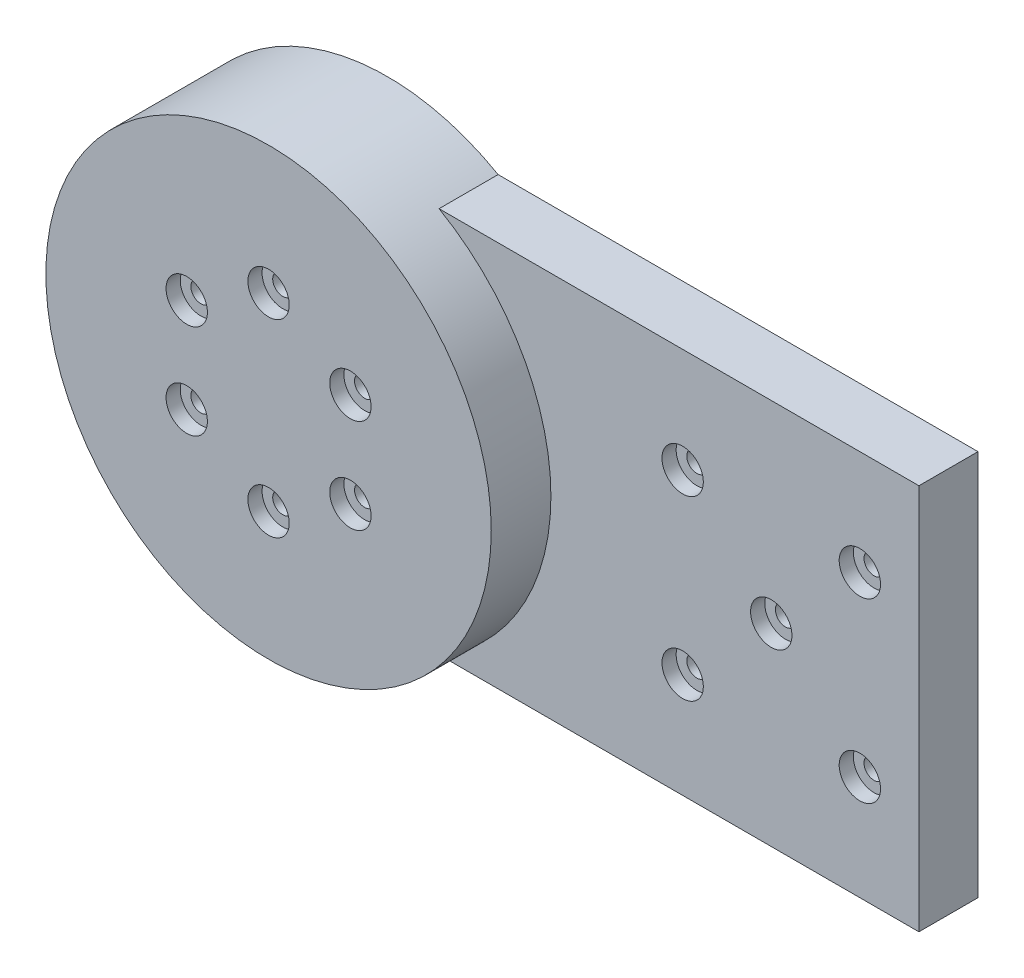
SolidWorks part; units mm, degrees
material "6063-T5"
ref_plane "Front" through (0, 0, 0) normal (0, 0, 1) x (1, 0, 0)
ref_plane "Top" through (0, 0, 0) normal (0, 1, 0) x (1, 0, 0)
ref_plane "Right" through (0, 0, 0) normal (1, 0, 0) x (0, 0, -1)
sketch "Croquis1" plane through (0, 0, 0) normal (0, 0, 1) x (1, 0, 0)
  circle A0 centre (0, 0) radius 37.7
  dimension "D1" = 75.4
extrude "Saliente-Extruir1" add sketch "Croquis1" along normal blind 7
hole_wizard "Refrentado para tornillo con cabeza troncocónica de M31" positions "Croquis2" profile "Croquis3" counterbore size "M3" standard "Ansi Metric" end condition up to next
sketch "Croquis2" plane through (0, 0, 7) normal (0, 0, 1) x (1, 0, 0)
  line L0 (0, -3.85) -> (0, 3.85) construction
  line L1 (3.85, 0) -> (-3.85, 0) construction
  point P0 (0, 16)
  point P11 (13.8564, 8)
  point P12 (13.8564, -8)
  point P13 (0, -16)
  point P14 (-13.8564, -8)
  point P15 (-13.8564, 8)
  dimension "D1" = 16
  dimension "D2" = 6
sketch "Croquis3" plane through (0, 16, 7) normal (1, 0, 0) x (0, -1, 0)
  line L0 (0, 0) -> (0, 7)
  line L1 (0, 7) -> (1.7, 7)
  line L3 (1.7, 7) -> (1.7, 2.4)
  line L4 (1.7, 2.4) -> (3.5, 2.4)
  line L5 (3.5, 2.4) -> (3.5, 0)
  line L7 (3.5, 0) -> (0, 0)
  line L11 (0, -6.35) -> (0, 107.95) construction
  dimension "Diámetro de taladro hasta el siguiente" = 3.4
  dimension "Profundidad de taladro hasta el siguiente" = 7
  dimension "Diámetro de refrentado" = 7
  dimension "Profundidad de refrentado" = 2.4
sketch "Croquis4" plane through (0, 0, 0) normal (0, 0, -1) x (-1, 0, 0)
  circle A0 centre (0, 0) radius 32.8
  circle A1 centre (0, 0) radius 37.7 construction
  circle A2 centre (0, 0) radius 37.7
  dimension "D1" = 65.6
extrude "Saliente-Extruir2" add sketch "Croquis4" along normal blind 13.1
sketch "Croquis5" plane through (0, 0, -13.1) normal (0, 0, -1) x (-1, 0, 0)
  line L0 (-18.7617, 32.7) -> (-100, 32.7)
  line L1 (-100, 32.7) -> (-100, -32.7)
  line L2 (-100, -32.7) -> (-18.7617, -32.7)
  line L3 (11.6038, 0) -> (-11.6038, 0) construction
  line L4 (0, 11.6038) -> (0, -11.6038) construction
  circle A0 centre (0, 0) radius 37.7 construction
  arc A1 (-18.7617, 32.7) -> (-18.7617, -32.7) centre (0, 0) ccw
  point P3 (-100, 0)
  dimension "D1" = 65.4
  dimension "D2" = 100
extrude "Saliente-Extruir3" add sketch "Croquis5" against normal blind 10
hole_wizard "Refrentado para tornillo con cabeza troncocónica de M32" positions "Croquis6" profile "Croquis7" counterbore size "M3" standard "Ansi Metric" end condition up to next
sketch "Croquis6" plane through (0, 0, -3.1) normal (0, 0, 1) x (1, 0, 0)
  line L1 (60, -15) -> (90, -15) construction
  line L2 (60, -15) -> (60, 15) construction
  line L3 (60, 15) -> (90, 15) construction
  line L4 (90, -15) -> (90, 15) construction
  line L5 (60, -15) -> (90, 15) construction
  line L6 (60, 15) -> (90, -15) construction
  line L7 (11.055, 0) -> (-11.055, 0) construction
  line L8 (100, 32.7) -> (100, -32.7) construction
  point P1 (75, 0)
  point P2 (90, 15)
  point P27 (60, -15)
  point P28 (60, 15)
  point P29 (90, -15)
  dimension "D1" = 25
  dimension "D2" = 30
sketch "Croquis7" plane through (75, 0, -3.1) normal (1, 0, 0) x (0, -1, 0)
  line L0 (0, 0) -> (0, 10)
  line L1 (0, 10) -> (1.7, 10)
  line L3 (1.7, 10) -> (1.7, 2.4)
  line L4 (1.7, 2.4) -> (3.5, 2.4)
  line L5 (3.5, 2.4) -> (3.5, 0)
  line L7 (3.5, 0) -> (0, 0)
  line L11 (0, -6.35) -> (0, 107.95) construction
  dimension "Diámetro de taladro hasta el siguiente" = 3.4
  dimension "Profundidad de taladro hasta el siguiente" = 10
  dimension "Diámetro de refrentado" = 7
  dimension "Profundidad de refrentado" = 2.4
